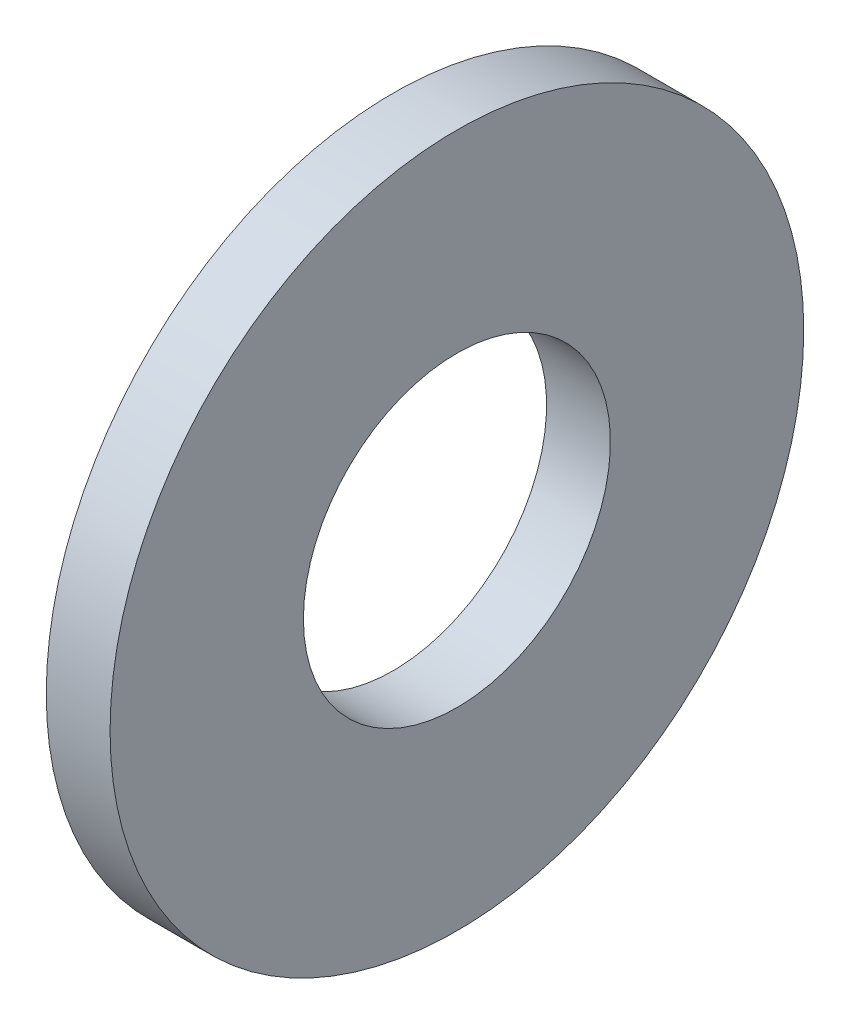
SolidWorks part; units mm, degrees
ref_plane "Plane1" through (0, 0, 0) normal (0, 0, 1) x (1, 0, 0)
ref_plane "Plane2" through (0, 0, 0) normal (0, 1, 0) x (1, 0, 0)
ref_plane "Plane3" through (0, 0, 0) normal (1, 0, 0) x (0, 0, -1)
sketch "Sketch1" plane through (0, 0, 0) normal (0, 0, 1) x (1, 0, 0)
  line L0 (-34.925, 0) -> (9.525, 0) construction
  line L1 (0, 11.065) -> (0, 25)
  line L2 (0, 25) -> (-4.6, 25)
  line L3 (-4.6, 25) -> (-4.6, 11.065)
  line L4 (-4.6, 11.065) -> (0, 11.065)
  dimension "Thickness" = 4.6
  dimension "Inside_dia" = 22.13
  dimension "Outside_dia" = 50
revolve "Base-Revolve" add sketch "Sketch1" angle 360 about L0
